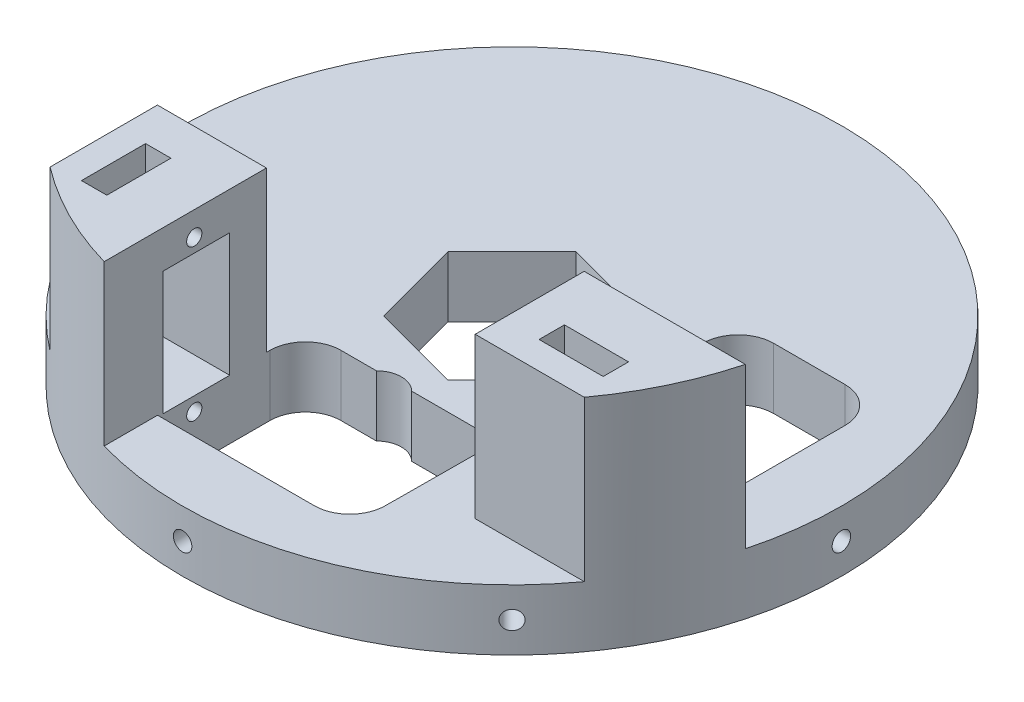
SolidWorks part; units mm, degrees
ref_plane "Front Plane" through (0, 0, 0) normal (0, 0, 1) x (1, 0, 0)
ref_plane "Top Plane" through (0, 0, 0) normal (0, 1, 0) x (1, 0, 0)
ref_plane "Right Plane" through (0, 0, 0) normal (1, 0, 0) x (0, 0, -1)
sketch "Sketch8" plane through (0, 0, 0) normal (0, 1, 0) x (1, 0, 0)
  line L0 (-17.9844, -38.525) -> (-17.9844, -18.7766)
  line L1 (-17.9844, -18.7766) -> (-39.4862, -18.7766)
  line L2 (-39.4862, -18.7766) -> (-39.4862, -51.6318)
  line L3 (-17.9844, -50.855) -> (-17.9844, -62.4625)
  line L4 (38.525, -16.775) -> (25.8978, -16.775)
  line L5 (20.0628, -25.8579) -> (20.0628, -38.275)
  line L6 (20.0628, -38.275) -> (52.5359, -38.275)
  line L7 (50.855, -16.775) -> (62.7981, -16.775)
  line L8 (-34.0744, -38.525) -> (-34.0744, -50.855)
  line L9 (-34.0744, -50.855) -> (-17.9844, -50.855)
  line L10 (-34.0744, -38.525) -> (-17.9844, -38.525)
  line L11 (38.525, -16.775) -> (38.525, -32.865)
  line L12 (38.525, -32.865) -> (50.855, -32.865)
  line L13 (50.855, -32.865) -> (50.855, -16.775)
  line L14 (-17.9844, -18.7766) -> (-17.9844, -18.7728)
  line L21 (-17.9844, -18.7728) -> (12.8574, -18.7728)
  line L22 (12.8574, -18.7728) -> (20.0628, -25.8579)
  line L23 (20.0995, -11.0735) -> (25.8978, -16.775)
  line L24 (20.0995, -11.0735) -> (20.0995, 21.1239)
  line L25 (20.0995, 21.1239) -> (53.8739, 21.1239)
  line L26 (53.8739, 21.1239) -> (53.8739, -16.775)
  line L27 (19.8645, -55.4325) -> (-17.9844, -55.4325)
  line L28 (20.0628, -25.8579) -> (19.8645, -55.4325)
  line L29 (25.8978, -16.775) -> (20.0628, -16.775)
  line L36 (20.0628, -16.775) -> (20.0628, -25.8579)
  line L38 (17.288, -4.6323) -> (12.6557, 12.6557)
  line L39 (12.6557, 12.6557) -> (-4.6323, 17.288)
  line L40 (-4.6323, 17.288) -> (-17.288, 4.6323)
  line L41 (-17.288, 4.6323) -> (-12.6557, -12.6557)
  line L42 (-12.6557, -12.6557) -> (4.6323, -17.288)
  line L43 (4.6323, -17.288) -> (17.288, -4.6323)
  circle A0 centre (0, 0) radius 65
  circle A1 centre (0, 0) radius 15.5 construction
extrude "Boss-Extrude1" add sketch "Sketch8" along normal blind 12 contours L7 A0 L2 L1 L14 L21 L22 L36 L29 L23 L24 L25 L26 L41 L40 L38 | L3 A0 L6 L5 L28 L27 region at (-9.8008, 0, -19.6664) region at (-17.1779, 0, 58.9475)
extrude "Boss-Extrude2" add sketch "Sketch8<4>" along normal blind 43.5 contours L2 A0 L3 L9 L8 L10 L0 L1 | L6 A0 L7 L13 L12 L11 L4 L29 L36 L5 region at (-28.927, 0, 36.5324) region at (37.7097, 0, 27.7555)
sketch "Sketch8<4>" plane through (0, 0, 0) normal (0, 1, 0) x (1, 0, 0) same geometry as "Sketch8"
sketch "Sketch9" plane through (0, 0, 0) normal (0, -1, 0) x (1, 0, 0)
  line L1 (-17.9844, 50.855) -> (-34.0744, 50.855)
  line L2 (-17.9844, 50.855) -> (-17.9844, 38.525)
  line L3 (-17.9844, 38.525) -> (-34.0744, 38.525)
  line L4 (-34.0744, 50.855) -> (-34.0744, 38.525)
extrude "Boss-Extrude3" add sketch "Sketch9" against normal blind 12.5
sketch "Sketch10" plane through (0, 0, 0) normal (0, -1, 0) x (1, 0, 0)
  line L1 (38.525, 32.865) -> (50.855, 32.865)
  line L2 (38.525, 32.865) -> (38.525, 16.775)
  line L3 (38.525, 16.775) -> (50.855, 16.775)
  line L4 (50.855, 32.865) -> (50.855, 16.775)
extrude "Boss-Extrude4" add sketch "Sketch10" against normal blind 12.5
sketch "Sketch11" plane through (0, 12.5, 0) normal (0, 1, 0) x (1, 0, 0)
  line L1 (38.525, -16.775) -> (50.855, -16.775)
  line L2 (38.525, -16.775) -> (38.525, -32.865)
  line L3 (38.525, -32.865) -> (50.855, -32.865)
  line L4 (50.855, -16.775) -> (50.855, -32.865)
  line L5 (-34.0744, -38.525) -> (-17.9844, -38.525)
  line L6 (-34.0744, -38.525) -> (-34.0744, -50.855)
  line L7 (-34.0744, -50.855) -> (-17.9844, -50.855)
  line L8 (-17.9844, -38.525) -> (-17.9844, -50.855)
  line M5 (38.525, -16.775) -> (38.525, -32.865)
  line M6 (38.525, -32.865) -> (50.855, -32.865)
  line M7 (50.855, -32.865) -> (50.855, -16.775)
  line M8 (50.855, -16.775) -> (38.525, -16.775)
extrude "Boss-Extrude5" add sketch "Sketch11" along normal blind 8.15 from offset 22.85 contours L8 L5 L6 L7 | M8 M5 M6 M7 region at (44.69, 12.5, 24.82) region at (-26.0294, 12.5, 44.69)
sketch "Sketch13" plane through (-17.9844, 0, 0) normal (1, 0, 0) x (0, 0, -1)
  line L1 (-38.525, 35.35) -> (-37.7004, 35.35)
  line L2 (-38.525, 35.35) -> (-38.525, 12.5)
  line L3 (-38.525, 12.5) -> (-37.7004, 12.5)
  line L4 (-37.7004, 35.35) -> (-37.7004, 12.5)
sketch "Sketch21" plane through (0, 12, 0) normal (0, 1, 0) x (1, 0, 0)
  line L0 (12.8574, -18.7728) -> (20.0628, -25.8579) construction
  line L1 (-17.9844, -18.7728) -> (16.9085, -18.7728)
  line L2 (-17.9844, -18.7728) -> (-17.9844, -22.7562)
  line L3 (-17.9844, -22.7562) -> (16.9085, -22.7562)
  line L4 (16.9085, -18.7728) -> (16.9085, -22.7562)
  line L5 (20.0995, -11.0735) -> (25.8978, -16.775) construction
  line L6 (20.0995, 21.1239) -> (23.4973, 21.1239)
  line L7 (20.0995, 21.1239) -> (20.0995, -14.4146)
  line L8 (20.0995, -14.4146) -> (23.4973, -14.4146)
  line L9 (23.4973, 21.1239) -> (23.4973, -14.4146)
extrude "Boss-Extrude8" add sketch "Sketch21" against normal blind 12
extrude "Cut-Extrude1" cut sketch "Sketch13" against normal blind 16.09
sketch "Sketch14" plane through (0, 0, 16.775) normal (0, 0, -1) x (-1, 0, 0)
  line L0 (-38.525, 12.5) -> (-50.855, 12.5) construction
  line L1 (-38.525, 35.35) -> (-37.6092, 35.35)
  line L2 (-38.525, 35.35) -> (-38.525, 12.5)
  line L3 (-38.525, 12.5) -> (-37.6092, 12.5)
  line L4 (-37.6092, 35.35) -> (-37.6092, 12.5)
extrude "Cut-Extrude2" cut sketch "Sketch14" against normal blind 16.09
sketch "Sketch15" plane through (0, 0, 16.775) normal (0, 0, -1) x (-1, 0, 0)
  line L0 (-53.8739, 0) -> (-25.8978, 0) construction
  line L1 (-53.8739, 12) -> (-51.5739, 12)
  line L2 (-53.8739, 12) -> (-53.8739, 0)
  line L3 (-53.8739, 0) -> (-51.5739, 0)
  line L4 (-51.5739, 12) -> (-51.5739, 0)
  dimension "D1" = 2.3
extrude "Boss-Extrude6" add sketch "Sketch15" along normal blind 39.09
sketch "Sketch16" plane through (-17.9844, 0, 0) normal (1, 0, 0) x (0, 0, -1)
  line L0 (-55.4325, 0) -> (-22.7562, 0) construction
  line L1 (-55.4325, 12) -> (-51.9325, 12)
  line L2 (-55.4325, 12) -> (-55.4325, 0)
  line L3 (-55.4325, 0) -> (-51.9325, 0)
  line L4 (-51.9325, 12) -> (-51.9325, 0)
  dimension "D1" = 3.5
extrude "Boss-Extrude7" add sketch "Sketch16" along normal blind 39.09
sketch "Sketch17" plane through (0, 43.5, 0) normal (0, 1, 0) x (1, 0, 0)
  line L0 (20.0628, -38.275) -> (52.5359, -38.275) construction
  line L1 (20.0628, -16.775) -> (31.0134, -16.775)
  line L2 (20.0628, -16.775) -> (20.0628, -38.275)
  line L3 (20.0628, -38.275) -> (31.0134, -38.275)
  line L4 (31.0134, -16.775) -> (31.0134, -38.275)
  line L5 (-17.9844, -18.7766) -> (-17.9844, -62.4625) construction
  line L6 (-39.4862, -18.7766) -> (-17.9844, -18.7766)
  line L7 (-39.4862, -18.7766) -> (-39.4862, -30.4561)
  line L8 (-39.4862, -30.4561) -> (-17.9844, -30.4561)
  line L9 (-17.9844, -18.7766) -> (-17.9844, -30.4561)
extrude "Cut-Extrude3" cut sketch "Sketch17" against normal blind 31.5
sketch "Sketch18" plane through (0, 0, 0) normal (0, 0, 1) x (1, 0, 0)
  line L0 (52.5359, 12) -> (-17.9844, 12) construction
  circle A0 centre (0, 6) radius 1.825
  dimension "D1" = 6
extrude "Cut-Extrude4" cut sketch "Sketch18" against normal blind 11 from offset 65
pattern_circular "CirPattern1" count 8 over 360 about axis through (0, 12, 0) along (0, -1, 0) of "Cut-Extrude4"
sketch "Sketch19" plane through (0, 0, 16.775) normal (0, 0, -1) x (-1, 0, 0)
  circle A0 centre (-44.69, 38.75) radius 1.5
  circle A1 centre (-44.69, 8.95) radius 1.5
extrude "Cut-Extrude5" cut sketch "Sketch19" against normal blind 5
sketch "Sketch20" plane through (-17.9844, 0, 0) normal (1, 0, 0) x (0, 0, -1)
  circle A0 centre (-44.69, 38.75) radius 1.5
  circle A1 centre (-44.69, 8.95) radius 1.5
extrude "Cut-Extrude8" cut sketch "Sketch20" against normal blind 5
sketch "Sketch22" plane through (0, 43.5, 0) normal (0, 1, 0) x (1, 0, 0)
  line L0 (-34.0744, -50.855) -> (-34.0744, -37.7004) construction
  line L1 (-34.0744, -38.205) -> (-29.0744, -38.205)
  line L2 (-34.0744, -38.205) -> (-34.0744, -50.855)
  line L3 (-34.0744, -50.855) -> (-29.0744, -50.855)
  line L4 (-29.0744, -38.205) -> (-29.0744, -50.855)
  line L7 (-17.9844, -50.855) -> (-34.0744, -50.855) construction
  line L8 (50.855, -32.865) -> (37.6092, -32.865) construction
  line L9 (38.205, -32.865) -> (50.855, -32.865)
  line L10 (38.205, -32.865) -> (38.205, -27.865)
  line L11 (38.205, -27.865) -> (50.855, -27.865)
  line L12 (50.855, -32.865) -> (50.855, -27.865)
  line L13 (50.855, -16.775) -> (50.855, -32.865) construction
  dimension "D1" = 12.65
  dimension "D2" = 5
  dimension "D3" = 0
  dimension "D4" = 5
  dimension "D5" = 12.65
  dimension "D6" = 0
extrude "Cut-Extrude9" cut sketch "Sketch22" against normal blind 12
fillet "Fillet1" radius 7 4 edges at (51.5739, 6, -21.1239) (19.888, 6, 51.9325) (-17.9844, 6, 22.7562) (23.4973, 6, -21.1239)
sketch "Sketch23" plane through (0, 12, 0) normal (0, 1, 0) x (1, 0, 0)
  line L0 (-10.9844, -22.7562) -> (16.9085, -22.7562) construction
  line L1 (-3.9886, -22.7562) -> (2.962, -22.7562)
  arc A0 (-3.9886, -22.7562) -> (2.962, -22.7562) centre (-0.5133, -26.2315) cw
extrude "Cut-Extrude10" cut sketch "Sketch23" against normal blind 12
sketch "Sketch24" plane through (0, 12, 0) normal (0, 1, 0) x (1, 0, 0)
  line L0 (23.4973, -14.4146) -> (23.4973, 14.1239) construction
  line L1 (23.4973, -3.3016) -> (23.4973, 3.1566)
  arc A0 (23.4973, -3.3016) -> (23.4973, 3.1566) centre (26.7264, -0.0725) cw
extrude "Cut-Extrude11" cut sketch "Sketch24" against normal blind 12
sketch "Sketch25" plane through (0, 0, 16.775) normal (0, 0, -1) x (-1, 0, 0)
  line L0 (65, 12) -> (-65, 12) construction
  line L1 (-50.855, 35.35) -> (-37.6092, 35.35)
  line L2 (-50.855, 35.35) -> (-50.855, 35.9673)
  line L3 (-50.855, 35.9673) -> (-37.6092, 35.9673)
  line L4 (-37.6092, 35.35) -> (-37.6092, 35.9673)
  line L5 (-50.855, 12.5) -> (-37.6092, 12.5)
  line L6 (-50.855, 12.5) -> (-50.855, 12)
  line L7 (-50.855, 12) -> (-37.6092, 12)
  line L8 (-37.6092, 12.5) -> (-37.6092, 12)
extrude "Cut-Extrude12" cut sketch "Sketch25" against normal blind 16.09
sketch "Sketch26" plane through (-17.9844, 0, 0) normal (1, 0, 0) x (0, 0, -1)
  line L1 (-50.855, 35.35) -> (-37.7004, 35.35)
  line L2 (-50.855, 35.35) -> (-50.855, 36.0665)
  line L3 (-50.855, 36.0665) -> (-37.7004, 36.0665)
  line L4 (-37.7004, 35.35) -> (-37.7004, 36.0665)
  line L5 (-50.855, 12.5) -> (-37.7004, 12.5)
  line L6 (-50.855, 12.5) -> (-50.855, 11.7068)
  line L7 (-50.855, 11.7068) -> (-37.7004, 11.7068)
  line L8 (-37.7004, 12.5) -> (-37.7004, 11.7068)
extrude "Cut-Extrude13" cut sketch "Sketch26" against normal blind 16.09
